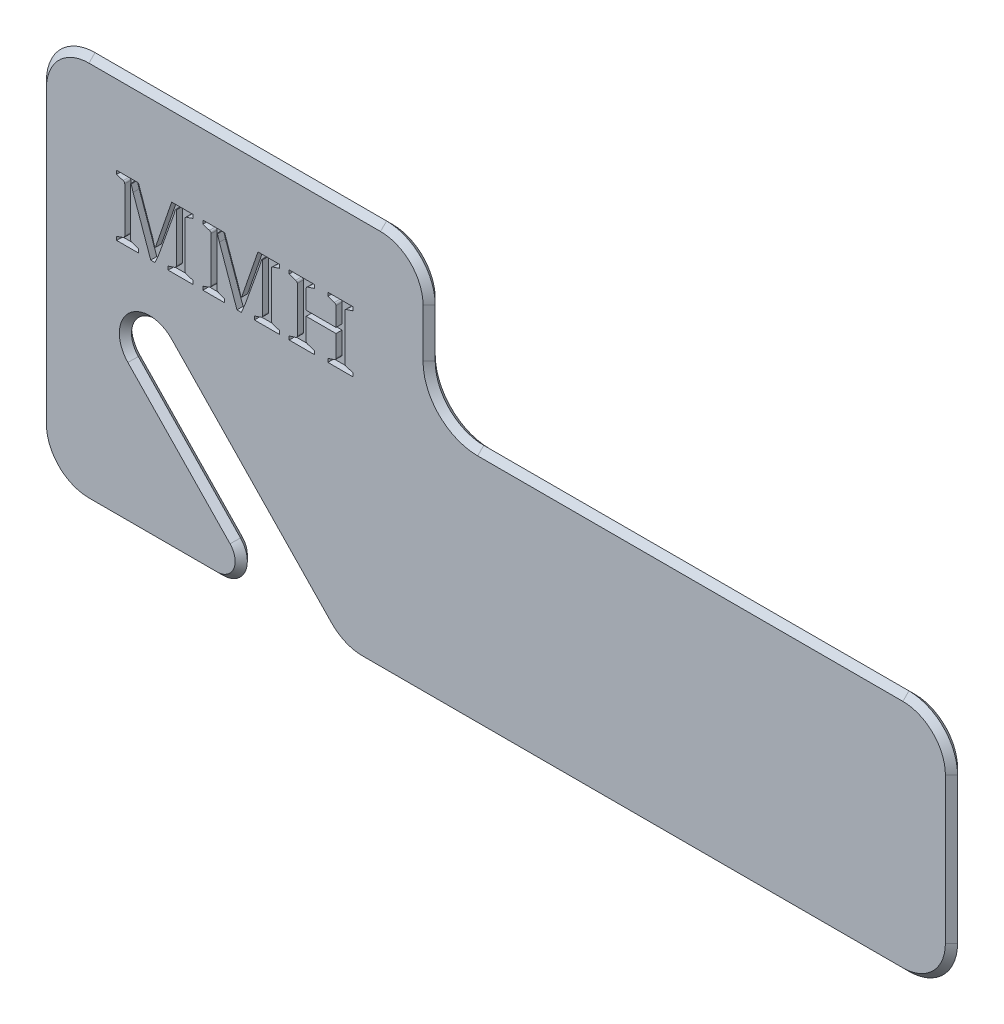
SolidWorks part; units mm, degrees
material "Plain Carbon Steel"
ref_plane "Front Plane" through (0, 0, 0) normal (0, 0, 1) x (1, 0, 0)
ref_plane "Top Plane" through (0, 0, 0) normal (0, 1, 0) x (1, 0, 0)
ref_plane "Right Plane" through (0, 0, 0) normal (1, 0, 0) x (0, 0, -1)
sketch "Sketch1" plane through (0, 0, 0) normal (0, 0, 1) x (1, 0, 0)
  line L0 (-6.985, 17.78) -> (-6.985, 22.86)
  line L1 (-42.545, -12.7) -> (42.545, -12.7)
  line L2 (-47.625, -7.62) -> (-47.625, 22.86)
  line L3 (-1.905, 12.7) -> (42.545, 12.7)
  line L4 (47.625, -7.62) -> (47.625, 7.62)
  line L5 (-47.625, -12.7) -> (47.625, 12.7) construction
  line L6 (-47.625, 12.7) -> (47.625, -12.7) construction
  line L11 (-12.065, 27.94) -> (-42.545, 27.94)
  arc A0 (-6.985, 17.78) -> (-1.905, 12.7) centre (-1.905, 17.78) ccw
  arc A1 (42.545, -12.7) -> (47.625, -7.62) centre (42.545, -7.62) ccw
  arc A2 (42.545, 12.7) -> (47.625, 7.62) centre (42.545, 7.62) cw
  arc A3 (-6.985, 22.86) -> (-12.065, 27.94) centre (-12.065, 22.86) ccw
  arc A4 (-42.545, -12.7) -> (-47.625, -7.62) centre (-42.545, -7.62) cw
  arc A5 (-42.545, 27.94) -> (-47.625, 22.86) centre (-42.545, 22.86) ccw
  point P0 (0, 0)
  point P19 (-6.985, 27.94)
  point P25 (-47.625, 27.94)
  point P26 (-44.2709, 8.8007)
  point P27 (0, 0)
  dimension "D5" = 5.08
  dimension "D1" = 95.25
  dimension "D2" = 25.4
  dimension "D3" = 40.64
  dimension "D4" = 40.64
extrude "Boss-Extrude1" add sketch "Sketch1" along normal mid plane 1.27
sketch "Sketch2" plane through (0, 0, 0.635) normal (0, 0, 1) x (1, 0, 0)
  line L0 (-36.195, 4.445) -> (-17.9561, -14.4634) construction
  line L1 (-34.3669, 6.2084) -> (-16.128, -12.7)
  line L2 (-38.0231, 2.6816) -> (-19.7843, -16.2268)
  line L3 (-42.545, -12.7) -> (42.545, -12.7) construction
  line L5 (-47.625, 22.86) -> (-47.625, -7.62) construction
  arc A0 (-34.3669, 6.2084) -> (-38.0231, 2.6816) centre (-36.195, 4.445) ccw
  arc A1 (-19.7843, -16.2268) -> (-16.128, -12.7) centre (-17.9561, -14.4634) ccw
  point P2 (-27.0756, -5.0092)
  dimension "D1" = 2.54
  dimension "D2" = 17.145
  dimension "D3" = 11.43
  dimension "D4" = 29.6689
extrude "Cut-Extrude1" cut sketch "Sketch2" against normal through all
fillet "Fillet1" radius 2.54 1 edges at (-23.1862, -12.7, 0)
fillet "Fillet2" radius 5.08 1 edges at (-16.128, -12.7, 0)
chamfer "Chamfer1" distance 0.635 angle 45 36 edges at (46.1371, -11.2121, -0.635) (47.625, 0, -0.635) (46.1371, 11.2121, -0.635) (20.32, 12.7, -0.635) (-5.4971, 14.1879, -0.635) (-6.985, 20.32, -0.635) (-8.4729, 26.4521, -0.635) (-27.305, 27.94, -0.635) (-46.1371, 26.4521, -0.635) (-47.625, 7.62, -0.635) (-46.1371, -11.2121, -0.635) (-35.8552, -12.7, -0.635) (-26.8275, -11.1531, -0.635) (-32.6802, -2.8575, -0.635) (-37.9584, 6.2731, -0.635) (-25.9966, -2.4692, -0.635) (-15.9562, -12.2956, -0.635) (14.2875, -12.7, -0.635) (-6.985, 20.32, 0.635) (-8.4729, 26.4521, 0.635) (-5.4971, 14.1879, 0.635) (-27.305, 27.94, 0.635) (20.32, 12.7, 0.635) (-46.1371, 26.4521, 0.635) (46.1371, 11.2121, 0.635) (-47.625, 7.62, 0.635) (47.625, 0, 0.635) (-46.1371, -11.2121, 0.635) (46.1371, -11.2121, 0.635) (-35.8552, -12.7, 0.635) (14.2875, -12.7, 0.635) (-26.8275, -11.1531, 0.635) (-15.9562, -12.2956, 0.635) (-32.6802, -2.8575, 0.635) (-37.9584, 6.2731, 0.635) (-25.9966, -2.4692, 0.635)
sketch "Sketch3" plane through (0, 0, 0.635) normal (0, 0, 1) x (1, 0, 0)
  line L2 (-46.99, 12.7) -> (-7.62, 12.7) construction
  line L3 (-46.99, 22.86) -> (-46.99, -7.62) construction
  text T0 "MMH" font "Sitka Text" height 6.35
extrude "Cut-Extrude2" cut sketch "Sketch3" against normal blind 0.635
